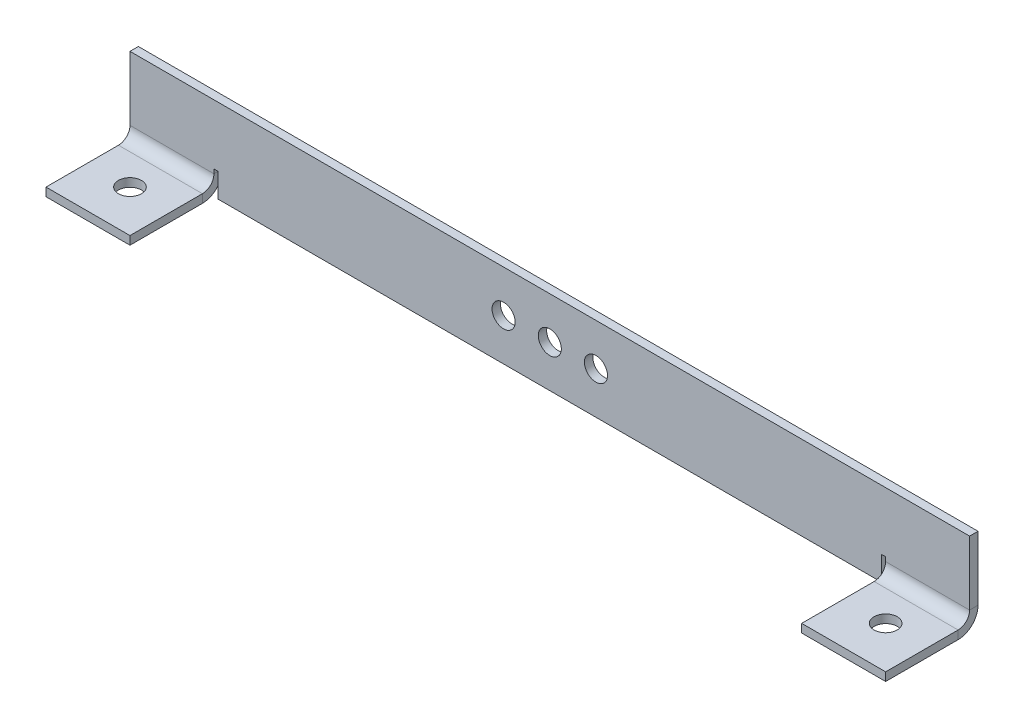
SolidWorks part; units mm, degrees
note: The reader was unsure of these and kept them because the rebuilt part matched: flange length of "边线-法兰1".
ref_plane "前视基准面" through (0, 0, 0) normal (0, 0, 1) x (1, 0, 0)
ref_plane "上视基准面" through (0, 0, 0) normal (0, 1, 0) x (1, 0, 0)
ref_plane "右视基准面" through (0, 0, 0) normal (1, 0, 0) x (0, 0, -1)
sketch "草图1" plane through (0, 0, 0) normal (0, 0, 1) x (1, 0, 0)
  line L0 (0, 0) -> (0, 58.0468) construction
  line L1 (-100, -20) -> (-100, 0)
  line L2 (100, -20) -> (100, 0)
  line L3 (-100, 0) -> (100, 0)
  line L5 (0, 0) -> (100, 0) construction
  line L9 (100, -20) -> (-100, -20)
  point P13 (0, -20)
  dimension "D1" = 20
  dimension "D3" = 100
base flange "基体-法兰1" sketch "草图1" thickness 2 reverse thickness direction no parameters "D1"=2.7366
edge flange "边线-法兰1" sketch "草图8" flange angle 90 flange length 22 flange position material inside bend radius 2.7366 thickness 2 relief rectangular parameters "D6"=10
sketch "草图8" plane through (0, -20, 0) normal (0, 1, 0) x (-1, 0, 0)
  line L2 (80, 0) -> (80, 20)
  line L3 (80, 20) -> (100, 20)
  line L4 (100, 20) -> (100, 0)
  line L10 (100, 0) -> (-100, 0) construction
  line L11 (100, 0) -> (80, 0)
  dimension "D1" = 20
  dimension "D2" = 20
bend "边线折弯1" bend radius 2.7366 bend angle 90 parameters "D5"=1
sketch "草图10" plane through (0, -18, 0) normal (0, 1, 0) x (1, 0, 0)
  line L0 (-100, -20) -> (-80, -20) construction
  line L1 (-80, -20) -> (-80, -2.7366) construction
  circle A0 centre (-90, -10) radius 2.75
  dimension "D3" = 5.5
  dimension "D1" = 10
  dimension "D2" = 10
extrude "切除-拉伸2" cut sketch "草图10" against normal blind 10 normal cut yes
mirror "镜向1" about plane through (0, 0, 0) normal (1, 0, 0) of "切除-拉伸2", "边线-法兰1"
bend "镜向折弯1" bend radius 2.7366 bend angle 90 parameters "D5"=2
sketch "草图11" plane through (0, 0, -2) normal (0, 0, -1) x (-1, 0, 0)
  line L0 (0, -10) -> (0, 0) construction
  line L2 (-100, 0) -> (100, 0) construction
  circle A0 centre (0, -10) radius 2.75
  circle A1 centre (-11, -10) radius 2.75
  circle A2 centre (11, -10) radius 2.75
  dimension "D1" = 5.5
  dimension "D2" = 10
  dimension "D3" = 11
extrude "切除-拉伸3" cut sketch "草图11" against normal blind 10 normal cut yes
sketch "折弯-线1" plane through (0, 0, 0) normal (0, 1, 0) x (1, 0, 0)
sketch "边界框1" plane through (0, 0, 0) normal (0, 1, 0) x (1, 0, 0)
sheet metal parameters "钣金6" thickness 2 parameters "D1"=2.7366
flat pattern "平板型式6" [suppressed]
sketch "折弯-线2" plane through (0, 0, 0) normal (0, 1, 0) x (1, 0, 0)
sketch "边界框2" [suppressed] plane through (0, 0, 0) normal (0, 1, 0) x (1, 0, 0)
sheet metal parameters "钣金7" thickness 2 parameters "D1"=2.7366
flat pattern "平板型式6" [suppressed]
sketch "折弯-线2" plane through (0, 0, 0) normal (0, 1, 0) x (1, 0, 0)
sketch "边界框2" [suppressed] plane through (0, 0, 0) normal (0, 1, 0) x (1, 0, 0)
bend of the flat pattern "展开-<边线折弯1>1"
sheet metal parameters "钣金8" thickness 2 parameters "D1"=2.7366
flat pattern "平板型式6" [suppressed]
sketch "折弯-线2" plane through (0, 0, 0) normal (0, 1, 0) x (1, 0, 0)
sketch "边界框2" [suppressed] plane through (0, 0, 0) normal (0, 1, 0) x (1, 0, 0)
bend of the flat pattern "展开-<边线折弯1>1"
bend of the flat pattern "展开-<镜向折弯1>1"
sheet metal parameters "钣金10" thickness 2 parameters "D1"=2.7366
flat pattern "平板型式6" [suppressed]
sketch "折弯-线2" plane through (0, 0, 0) normal (0, 1, 0) x (1, 0, 0)
sketch "边界框2" [suppressed] plane through (0, 0, 0) normal (0, 1, 0) x (1, 0, 0)
bend of the flat pattern "展开-<边线折弯1>1"
sheet metal parameters "钣金11" thickness 2 parameters "D1"=2.7366
flat pattern "平板型式6" [suppressed]
sketch "折弯-线2" plane through (0, 0, 0) normal (0, 1, 0) x (1, 0, 0)
sketch "边界框2" [suppressed] plane through (0, 0, 0) normal (0, 1, 0) x (1, 0, 0)
bend of the flat pattern "展开-<边线折弯1>1"
bend of the flat pattern "展开-<镜向折弯1>1"
